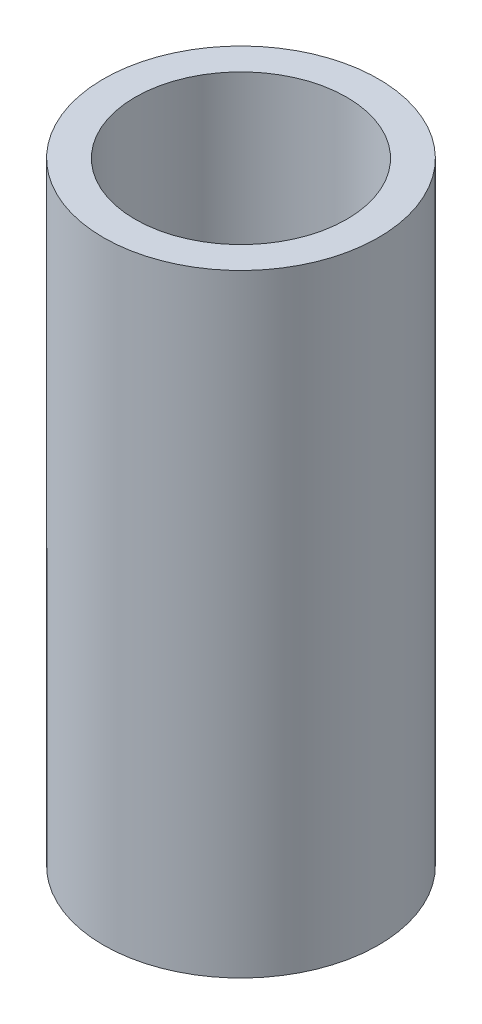
SolidWorks part; units mm, degrees
ref_plane "Front Plane" through (0, 0, 0) normal (0, 0, 1) x (1, 0, 0)
ref_plane "Top Plane" through (0, 0, 0) normal (0, 1, 0) x (1, 0, 0)
ref_plane "Right Plane" through (0, 0, 0) normal (1, 0, 0) x (0, 0, -1)
sketch "Sketch1" plane through (0, 0, 0) normal (0, 1, 0) x (1, 0, 0)
  circle A0 centre (0, 0) radius 32.5
  dimension "SLEEVE_OD" = 65
extrude "Boss-Extrude1" add sketch "Sketch1" along normal blind 144.8609
sketch "Sketch2" plane through (0, 0, 0) normal (0, 1, 0) x (1, 0, 0)
  circle A0 centre (0, 0) radius 25.0102
  dimension "BORE_D" = 50.0205
extrude "Cut-Extrude1" cut sketch "Sketch2" along normal through all
chamfer "Chamfer1" distance 3.9588 angle 45 rebuild error yes
